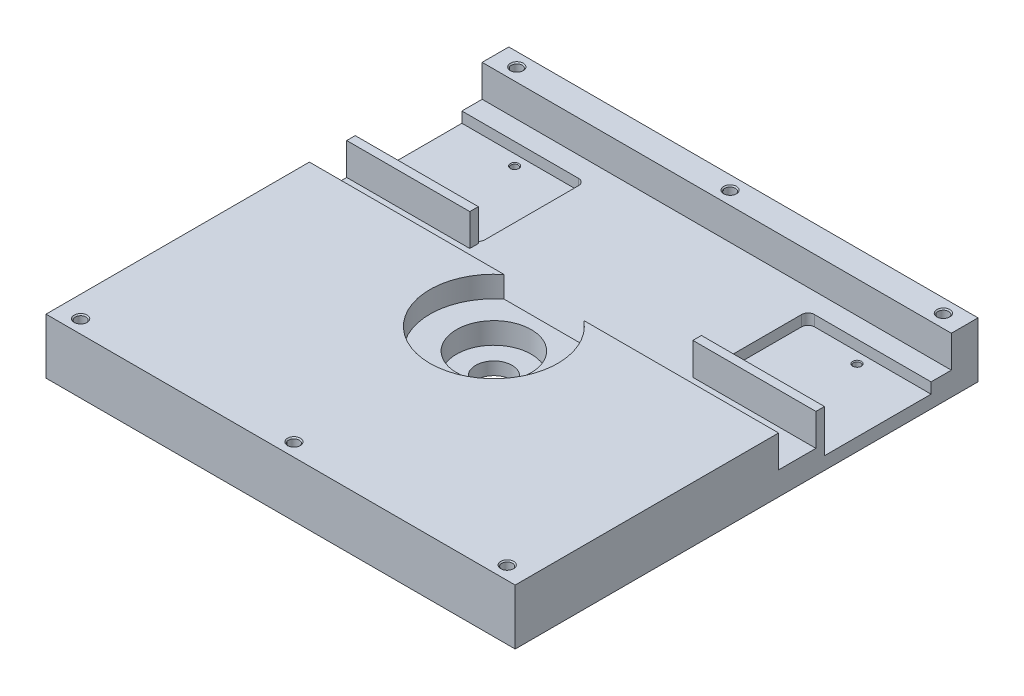
SolidWorks part; units mm, degrees
material "POM Acetal Copolymer"
ref_plane "Front Plane" through (0, 0, 0) normal (0, 0, 1) x (1, 0, 0)
ref_plane "Top Plane" through (0, 0, 0) normal (0, 1, 0) x (1, 0, 0)
ref_plane "Right Plane" through (0, 0, 0) normal (1, 0, 0) x (0, 0, -1)
sketch "Sketch1" plane through (0, 0, 0) normal (0, 1, 0) x (1, 0, 0)
  line L1 (-110, -108.5) -> (110, -108.5)
  line L2 (-110, -108.5) -> (-110, 108.5)
  line L3 (-110, 108.5) -> (110, 108.5)
  line L4 (110, -108.5) -> (110, 108.5)
  line L5 (-110, -108.5) -> (110, 108.5) construction
  line L6 (-110, 108.5) -> (110, -108.5) construction
  point P0 (0, 0)
  dimension "D1" = 217
  dimension "D2" = 220
extrude "Bloco (Bruto)" add sketch "Sketch1" along normal blind 26
sketch "Sketch2" plane through (0, 26, 0) normal (0, 1, 0) x (1, 0, 0)
  line L0 (110, -8.5) -> (-110, -8.5) construction
  line L1 (110, -108.5) -> (110, 108.5) construction
  line L2 (-110, 108.5) -> (-110, -108.5) construction
  line L3 (0, -108.5) -> (0, -8.5) construction
  line L4 (-110, -108.5) -> (110, -108.5) construction
  circle A0 centre (0, -8.5) radius 30
  circle A1 centre (0, -8.5) radius 17.5
  circle A2 centre (0, -8.5) radius 8.5
  dimension "D2" = 60
  dimension "D3" = 35
  dimension "D4" = 17
  dimension "D1" = 100
extrude "Furo Ø17 Passante" cut sketch "Sketch2" against normal through all contours A2 region at (0, 26, 8.5)
extrude "Rebaixo Ø35x20" cut sketch "Sketch2<3>" against normal blind 20 contours A1 A2 region at (-17.005, 26, 8.5)
sketch "Sketch2<3>" plane through (0, 26, 0) normal (0, 1, 0) x (1, 0, 0) same geometry as "Sketch2"
extrude "Rebaixo Ø60x10" cut sketch "Sketch2<4>" against normal blind 10 contours A0 A1 region at (-29.1515, 26, 8.5)
sketch "Sketch2<4>" plane through (0, 26, 0) normal (0, 1, 0) x (1, 0, 0) same geometry as "Sketch2"
sketch "Sketch3" plane through (0, 26, 0) normal (0, 1, 0) x (1, 0, 0)
  line L0 (110, -108.5) -> (110, 108.5) construction
  line L1 (110, 96) -> (-110, 96)
  line L2 (110, 96) -> (110, 15)
  line L3 (110, 15) -> (-110, 15)
  line L4 (-110, 96) -> (-110, 15)
  line L5 (-110, 108.5) -> (-110, -108.5) construction
  line L6 (110, 108.5) -> (-110, 108.5) construction
  line L7 (0, 96) -> (0, 15) construction
  line L8 (-110, 36.5) -> (-52.3, 36.5)
  line L9 (-110, 36.5) -> (-110, 32.5)
  line L10 (-110, 32.5) -> (-52.3, 32.5)
  line L11 (-52.3, 36.5) -> (-52.3, 32.5)
  line L12 (110, 32.5) -> (52.3, 32.5)
  line L13 (52.3, 36.5) -> (52.3, 32.5)
  line L14 (110, 36.5) -> (52.3, 36.5)
  line L15 (110, 36.5) -> (110, 32.5)
  circle M5 centre (0, -8.5) radius 30
  line M6 (110, -108.5) -> (110, 108.5)
  line M8 (-110, 108.5) -> (-110, -108.5)
  dimension "D1" = 12.5
  dimension "D2" = 81
  dimension "D3" = 4
  dimension "D4" = 57.7
  dimension "D5" = 17.5
extrude "Rebaixo 220x81x15" cut sketch "Sketch3" against normal blind 15 contours L7 L3 M5 | L7 L3 M5 | L1 L7 L3 L12 L13 L14 M5 M6 | L7 L1 L8 L11 L10 L3 M8 M5 region at (54.7589, 26, -56.4283) region at (-54.7589, 26, -56.4283) region at (7.1064, 26, -17.6258) region at (-7.1064, 26, -17.6258)
sketch "Sketch4" plane through (0, 11, 0) normal (0, 1, 0) x (1, 0, 0)
  line L0 (-110, 96) -> (-110, 36.5) construction
  line L1 (-110, 86.5) -> (-55.3, 86.5)
  line L2 (-110, 86.5) -> (-110, 36.5)
  line L3 (-110, 36.5) -> (-55.3, 36.5)
  line L4 (-52.3, 83.5) -> (-52.3, 39.5)
  line L5 (0, 96) -> (0, 15) construction
  line L6 (110, 96) -> (-110, 96) construction
  line L7 (110, 15) -> (-110, 15) construction
  line L8 (110, 36.5) -> (55.3, 36.5)
  line L9 (52.3, 83.5) -> (52.3, 39.5)
  line L10 (110, 86.5) -> (55.3, 86.5)
  line L11 (110, 86.5) -> (110, 36.5)
  arc A0 (-55.3, 36.5) -> (-52.3, 39.5) centre (-55.3, 39.5) ccw
  arc A1 (-55.3, 86.5) -> (-52.3, 83.5) centre (-55.3, 83.5) cw
  arc A4 (55.3, 36.5) -> (52.3, 39.5) centre (55.3, 39.5) cw
  arc A5 (55.3, 86.5) -> (52.3, 83.5) centre (55.3, 83.5) ccw
  point P9 (-52.3, 36.5)
  dimension "D2" = 3
  dimension "D1" = 50
extrude "Rebaixo - Encaixe Mancais" cut sketch "Sketch4" against normal blind 5 contours L2 L1 A1 L4 A0 L3 | L8 A4 L9 A5 L10 L11
sketch "Posição - Furos Mancais" plane through (0, 6, 0) normal (0, 1, 0) x (1, 0, 0)
  line L0 (-80.3, 86.5) -> (-80.3, 36.5) construction
  line L1 (-110, 86.5) -> (-55.3, 86.5) construction
  line L2 (-110, 36.5) -> (-52.3, 36.5) construction
  line L3 (-110, 86.5) -> (-110, 36.5) construction
  line L4 (0, 96) -> (0, 15) construction
  line L5 (110, 96) -> (-110, 96) construction
  line L6 (110, 15) -> (-110, 15) construction
  circle A0 centre (-80.3, 81.5) radius 1.65
  circle A1 centre (-80.3, 41.5) radius 1.65
  circle A2 centre (80.3, 41.5) radius 1.65
  circle A3 centre (80.3, 81.5) radius 1.65
  dimension "D2" = 3.3
  dimension "D3" = 40
  dimension "D4" = 5
  dimension "D1" = 29.7
sketch "Posição - Furos Apoio" plane through (0, 26, 0) normal (0, 1, 0) x (1, 0, 0)
  line L0 (-110, -102.25) -> (110, -102.25) construction
  line L1 (-110, 15) -> (-110, -108.5) construction
  line L2 (110, -108.5) -> (110, 15) construction
  line L3 (-110, -108.5) -> (110, -108.5) construction
  line L4 (110, 0) -> (-110, 0) construction
  line L6 (-110, 102.25) -> (110, 102.25) construction
  line L7 (0, -102.25) -> (0, -0.25) construction
  circle A0 centre (-100, -102.25) radius 2.5
  circle A1 centre (0, -102.25) radius 2.5
  circle A2 centre (100, -102.25) radius 2.5
  circle A3 centre (-100, 102.25) radius 2.5
  circle A4 centre (0, 102.25) radius 2.5
  circle A5 centre (100, 102.25) radius 2.5
  dimension "D2" = 110
  dimension "D3" = 100
  dimension "D4" = 100
  dimension "D5" = 5
  dimension "D1" = 6.25
  dimension "D6" = 108.5
hole_wizard "M6x1.0 - Furos Apoio" positions "Sketch7" profile "Sketch8" tap size "M6x1.0" standard "ANSI Metric"
sketch "Sketch7" plane through (0, 26, 0) normal (0, 1, 0) x (1, 0, 0)
  point P0 (-100, -102.25)
  point P3 (0, -102.25)
  point P6 (100, -102.25)
  point P9 (-100, 102.25)
  point P12 (0, 102.25)
  point P15 (100, 102.25)
sketch "Sketch8" plane through (-100, 26, 102.25) normal (1, 0, 0) x (0, 0, 1)
  line L0 (0, 0) -> (0, 18.5022)
  line L1 (0, 18.5022) -> (2.5, 17)
  line L2 (2.5, 17) -> (2.5, 0.525)
  line L3 (2.5, 0.525) -> (3.025, 0)
  line L5 (3.025, 0) -> (0, 0)
  line L6 (-2.5, 0.525) -> (-3.025, 0) construction
  line L10 (0, 18.5022) -> (-2.5, 17) construction
  line L11 (0, -6.35) -> (0, 107.95) construction
  dimension "Tap Drill Dia." = 5
  dimension "Tap Drill Depth" = 17
  dimension "Near C'Sink Dia." = 6.05
  dimension "Near C'Sink Angle" = 90
  dimension "Drill Angle" = 118
cosmetic thread "Hole Thread1" parameters "D1"=12, "D2"=6
cosmetic thread "Hole Thread2" parameters "D1"=12, "D2"=6
cosmetic thread "Hole Thread3" parameters "D1"=12, "D2"=6
cosmetic thread "Hole Thread4" parameters "D1"=12, "D2"=6
cosmetic thread "Hole Thread5" parameters "D1"=12, "D2"=6
cosmetic thread "Hole Thread6" parameters "D1"=12, "D2"=6
hole_wizard "M4x0.7 Tapped Hole1" positions "Sketch9" profile "Sketch10" tap size "M4x0.7" standard "ANSI Metric"
sketch "Sketch9" plane through (0, 6, 0) normal (0, 1, 0) x (1, 0, 0)
  point P0 (-80.3, 81.5)
  point P3 (-80.3, 41.5)
  point P6 (80.3, 81.5)
  point P9 (80.3, 41.5)
sketch "Sketch10" plane through (-80.3, 6, -81.5) normal (1, 0, 0) x (0, 0, 1)
  line L0 (0, 0) -> (0, 12.4914)
  line L1 (0, 12.4914) -> (1.65, 11.5)
  line L2 (1.65, 11.5) -> (1.65, 0.375)
  line L3 (1.65, 0.375) -> (2.025, 0)
  line L5 (2.025, 0) -> (0, 0)
  line L6 (-1.65, 0.375) -> (-2.025, 0) construction
  line L10 (0, 12.4914) -> (-1.65, 11.5) construction
  line L11 (0, -6.35) -> (0, 107.95) construction
  dimension "Tap Drill Dia." = 3.3
  dimension "Tap Drill Depth" = 11.5
  dimension "Near C'Sink Dia." = 4.05
  dimension "Near C'Sink Angle" = 90
  dimension "Drill Angle" = 118
cosmetic thread "Hole Thread7" parameters "D1"=8, "D2"=4
cosmetic thread "Hole Thread8" parameters "D1"=8, "D2"=4
cosmetic thread "Hole Thread9" parameters "D1"=8, "D2"=4
cosmetic thread "Hole Thread10" parameters "D1"=8, "D2"=4
